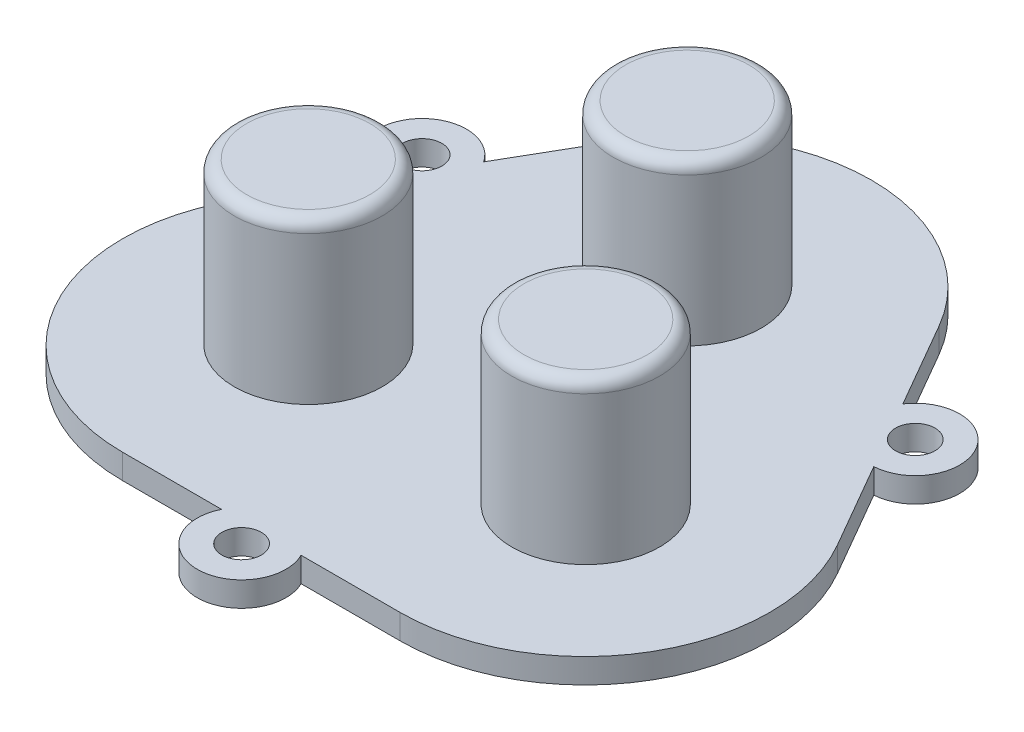
SolidWorks part; units mm, degrees
ref_plane "Front Plane" through (0, 0, 0) normal (0, 0, 1) x (1, 0, 0)
ref_plane "Top Plane" through (0, 0, 0) normal (0, 1, 0) x (1, 0, 0)
ref_plane "Right Plane" through (0, 0, 0) normal (1, 0, 0) x (0, 0, -1)
sketch "Sketch5" plane through (0, 0, 0) normal (0, 1, 0) x (1, 0, 0)
  line L3 (-11.25, -22.1428) -> (-3.2249, -22.1428)
  line L4 (3.2249, -22.1428) -> (11.25, -22.1428)
  line L5 (24.2404, 0.3572) -> (20.2278, 7.3072)
  line L6 (17.0029, 12.8928) -> (12.9904, 19.8428)
  line L7 (-12.9904, 19.8428) -> (-17.0029, 12.8928)
  line L8 (-20.2278, 7.3072) -> (-24.2404, 0.3572)
  arc A3 (-3.2249, -22.1428) -> (3.2249, -22.1428) centre (0, -23.7428) ccw
  arc A4 (11.25, -22.1428) -> (24.2404, 0.3572) centre (11.25, -7.1428) ccw
  arc A5 (20.2278, 7.3072) -> (17.0029, 12.8928) centre (20.001, 10.9) ccw
  arc A6 (12.9904, 19.8428) -> (-12.9904, 19.8428) centre (0, 12.3428) ccw
  arc A7 (-17.0029, 12.8928) -> (-20.2278, 7.3072) centre (-20.001, 10.9) ccw
  arc A8 (-24.2404, 0.3572) -> (-11.25, -22.1428) centre (-11.25, -7.1428) ccw
  circle A9 centre (20.001, 10.9) radius 1.6
  circle A10 centre (0, -23.7428) radius 1.6
  circle A11 centre (-20.001, 10.9) radius 1.6
extrude "Boss-Extrude2" add sketch "Sketch5" along normal blind 2
sketch "Sketch6" plane through (0, 0, 0) normal (0, 1, 0) x (1, 0, 0)
  circle A12 centre (-0.06, 12.4628) radius 6
  circle A13 centre (11.19, -7.0227) radius 6
  circle A14 centre (-11.31, -7.0227) radius 6
extrude "Boss-Extrude3" add sketch "Sketch6" along normal blind 15
fillet "Fillet1" radius 1 3 edges at (-11.31, 15, 13.0227) (11.19, 15, 13.0227) (-0.06, 15, -6.4628)
